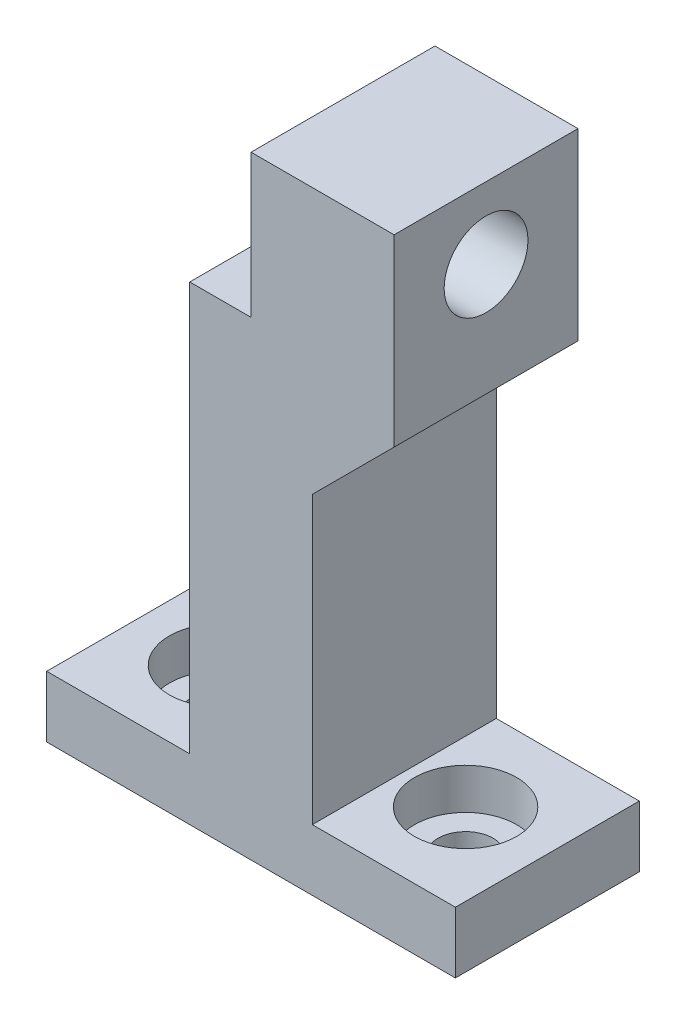
SolidWorks part; units mm, degrees
ref_plane "Front Plane" through (0, 0, 0) normal (0, 0, 1) x (1, 0, 0)
ref_plane "Top Plane" through (0, 0, 0) normal (0, 1, 0) x (1, 0, 0)
ref_plane "Right Plane" through (0, 0, 0) normal (1, 0, 0) x (0, 0, -1)
sketch "Sketch1" plane through (0, 0, 0) normal (0, 1, 0) x (1, 0, 0)
  line L1 (-10, -4.5) -> (10, -4.5)
  line L2 (-10, -4.5) -> (-10, 4.5)
  line L3 (-10, 4.5) -> (10, 4.5)
  line L4 (10, -4.5) -> (10, 4.5)
  line L5 (-10, -4.5) -> (10, 4.5) construction
  line L6 (-10, 4.5) -> (10, -4.5) construction
  point P0 (0, 0)
  dimension "D1" = 9
  dimension "D2" = 20
extrude "Boss-Extrude1" add sketch "Sketch1" along normal blind 3
sketch "Sketch2" plane through (0, 3, 0) normal (0, 1, 0) x (1, 0, 0)
  line L0 (-6, 0) -> (6, 0) construction
  circle A0 centre (-6, 0) radius 1.35
  circle A1 centre (6, 0) radius 1.35
  point P4 (0, 0)
  dimension "D1" = 2.7
  dimension "D2" = 12
extrude "Cut-Extrude1" cut sketch "Sketch2" against normal through all
sketch "Sketch3" plane through (0, 3, 0) normal (0, 1, 0) x (1, 0, 0)
  circle A0 centre (-6, 0) radius 2.5
  circle A1 centre (6, 0) radius 2.5
  dimension "D1" = 5
extrude "Cut-Extrude2" cut sketch "Sketch3" against normal blind 2
sketch "Sketch4" plane through (0, 3, 0) normal (0, 1, 0) x (1, 0, 0)
  line L0 (10, 4.5) -> (-10, 4.5) construction
  line L1 (-3, -4.5) -> (3, -4.5)
  line L2 (-3, -4.5) -> (-3, 4.5)
  line L3 (-3, 4.5) -> (3, 4.5)
  line L4 (3, -4.5) -> (3, 4.5)
  line L5 (-3, -4.5) -> (3, 4.5) construction
  line L6 (-3, 4.5) -> (3, -4.5) construction
  point P0 (0, 0)
  dimension "D1" = 6
extrude "Boss-Extrude2" add sketch "Sketch4" along normal blind 20
sketch "Sketch7" plane through (0, 23, 0) normal (0, 1, 0) x (1, 0, 0)
  line L0 (-3, -4.5) -> (3, -4.5) construction
  line L1 (3, 4.5) -> (0, 4.5)
  line L2 (3, 4.5) -> (3, -4.5)
  line L3 (3, -4.5) -> (0, -4.5)
  line L4 (0, 4.5) -> (0, -4.5)
extrude "Boss-Extrude5" add sketch "Sketch7" along normal blind 7
sketch "Sketch8" plane through (3, 0, 0) normal (1, 0, 0) x (0, 0, -1)
  line L0 (-4.5, 30) -> (-4.5, 3) construction
  line L1 (4.5, 30) -> (-4.5, 30)
  line L2 (4.5, 30) -> (4.5, 21)
  line L3 (4.5, 21) -> (-4.5, 21)
  line L4 (-4.5, 30) -> (-4.5, 21)
extrude "Boss-Extrude6" add sketch "Sketch8" along normal blind 4
chamfer "Chamfer1" distance 4 angle 45 1 edges at (3, 21, 0)
sketch "Sketch9" plane through (0, 0, 0) normal (-1, 0, 0) x (0, 0, 1)
  line L0 (-4.5, 30) -> (4.5, 23) construction
  circle A0 centre (0, 26.5) radius 2.05
  dimension "D1" = 4.1
extrude "Cut-Extrude3" cut sketch "Sketch9" against normal through all
